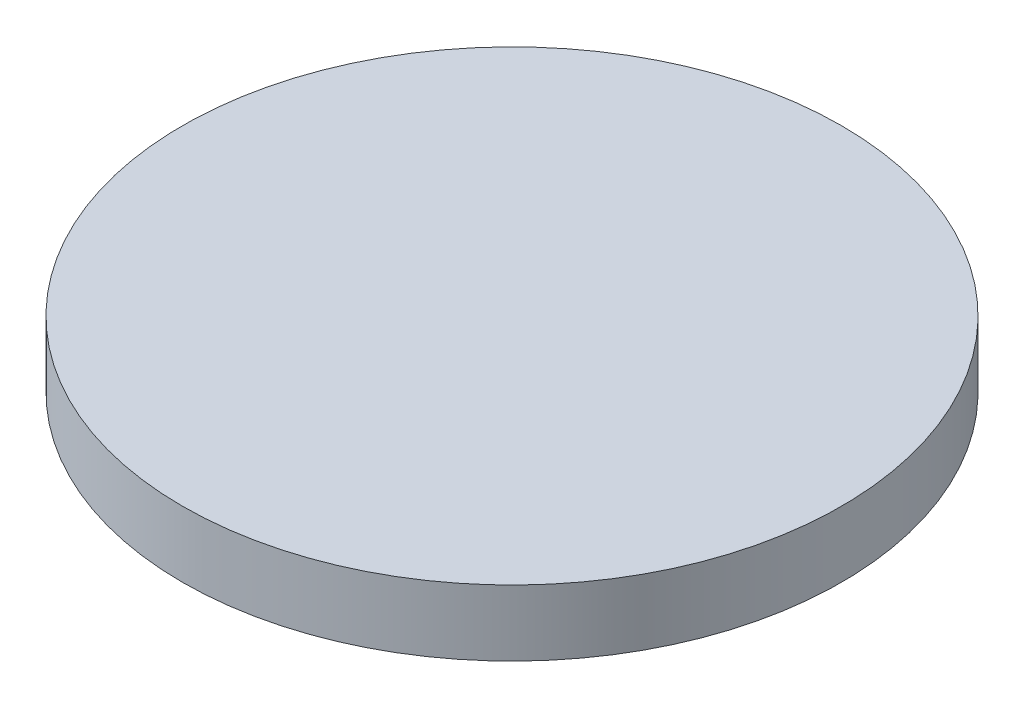
SolidWorks part; units mm, degrees
ref_plane "Front" through (0, 0, 0) normal (0, 0, 1) x (1, 0, 0)
ref_plane "Top" through (0, 0, 0) normal (0, 1, 0) x (1, 0, 0)
ref_plane "Right" through (0, 0, 0) normal (1, 0, 0) x (0, 0, -1)
sketch "Sketch1" plane through (0, 0, 0) normal (0, 1, 0) x (1, 0, 0)
  circle A0 centre (0, 0) radius 50
  dimension "D1" = 100
extrude "Boss-Extrude1" add sketch "Sketch1" along normal blind 10
